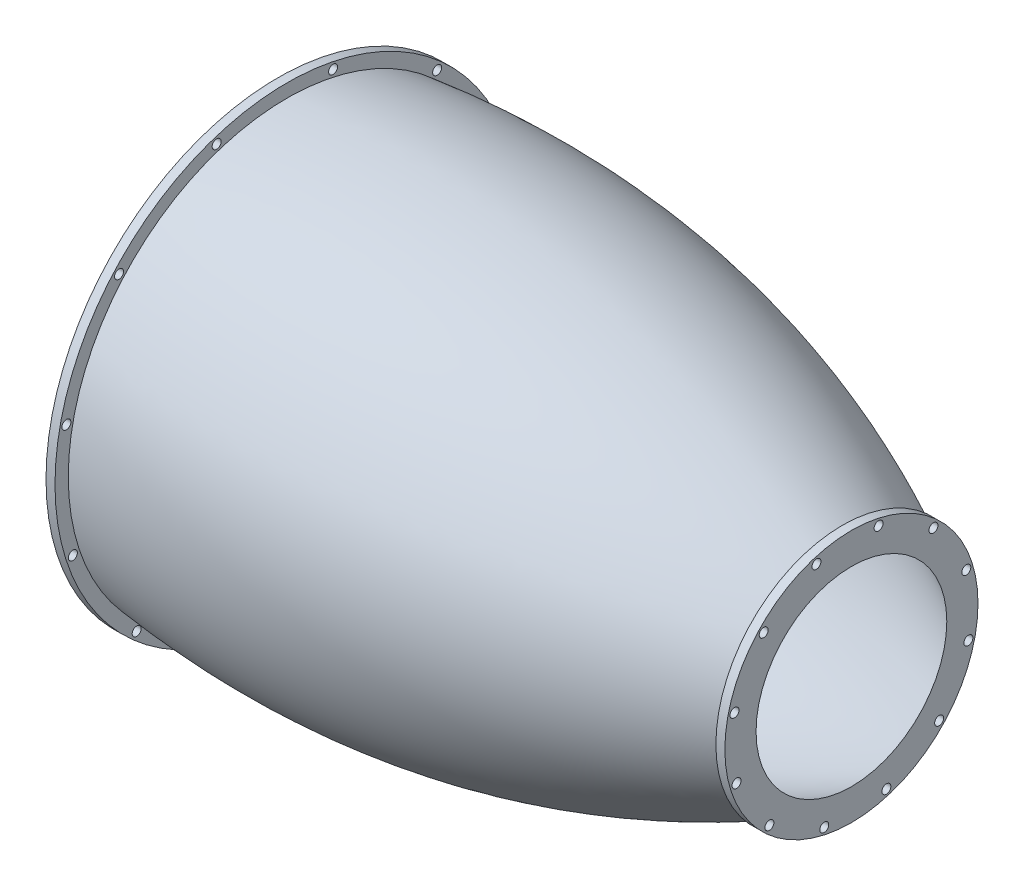
SolidWorks part; units mm, degrees
material "Copper"
ref_plane "Front Plane" through (0, 0, 0) normal (0, 0, 1) x (1, 0, 0)
ref_plane "Top Plane" through (0, 0, 0) normal (0, 1, 0) x (1, 0, 0)
ref_plane "Right Plane" through (0, 0, 0) normal (1, 0, 0) x (0, 0, -1)
sketch "Sketch1" plane through (0, 0, 0) normal (0, 0, 1) x (1, 0, 0)
  line L0 (-1229.8282, 0) -> (1426.3964, 0) construction
  line L1 (0, -63.5) -> (0, 63.5) construction
  line L2 (0, 0) -> (500, 0) construction
  line L3 (500, -330.2) -> (500, 330.2) construction
  line L5 (500, 339.09) -> (500, 330.2)
  line L6 (0, -72.39) -> (0, -63.5)
  line L7 (500, -339.09) -> (500, -330.2)
  line L8 (-412.8242, -144.8099) -> (-412.8242, 144.8099) construction
  line L9 (-412.8242, 144.8099) -> (-412.8242, 153.6999)
  line L10 (-412.8242, -144.8099) -> (-412.8242, -153.6999)
  spline S0 degree 2 poles (0, 63.5) (163.7773, 321.6338) (500, 330.2) knots 0 0 0 1 1 1
  spline S1 degree 2 poles (0, -63.5) (163.7773, -321.6338) (500, -330.2) knots 0 0 0 1 1 1
  spline S2 degree 2 poles (0, -72.39) (163.7773, -330.5238) (500, -339.09) knots 0 0 0 1 1 1
  spline S3 degree 2 poles (0, -63.5) (163.7773, -321.6338) (500, -330.2) knots 0 0 0 1 1 1
  spline S4 degree 2 poles (0, 72.39) (163.7773, 330.5238) (500, 339.09) knots 0 0 0 1 1 1
  spline S5 degree 2 poles (0, 63.5) (-192.2835, 162.6782) (-412.8242, 144.8099) knots 0 0 0 1 1 1
  spline S6 degree 2 poles (0, -63.5) (-192.2835, -162.6782) (-412.8242, -144.8099) knots 0 0 0 1 1 1
  spline S7 degree 2 poles (0, -72.39) (-189.3535, -181.7828) (-412.8242, -153.6999) knots 0 0 0 1 1 1
  spline S9 degree 2 poles (0, 72.39) (-189.3535, 181.7828) (-412.8242, 153.6999) knots 0 0 0 1 1 1
  point P8 (0, 0)
  point P14 (500, 0)
  point P22 (-412.8242, 0)
  dimension "D4" = 8.89
  dimension "D1" = 127
  dimension "D2" = 500
  dimension "D3" = 660.4
  dimension "D5" = 8.89
  dimension "D6" = 8.89
  dimension "D7" = 289.6197
revolve "Revolve3" add sketch "Sketch1" angle 360 about L0 region at (490.4648, 334.645, 0)
ref_plane "Plane1" through (0, 0, 0) normal (1, 0, 0) x (0, 0, -1)
ref_plane "Plane2" through (-7.62, 0, 0) normal (-1, 0, 0) x (0, 0, 1)
sketch "Sketch4" plane through (-7.62, 0, 0) normal (-1, 0, 0) x (0, 0, 1)
  line L1 (-1213.2286, 638.9142) -> (1085.9115, 638.9142)
  line L2 (-1213.2286, 638.9142) -> (-1213.2286, -445.9528)
  line L3 (-1213.2286, -445.9528) -> (1085.9115, -445.9528)
  line L4 (1085.9115, 638.9142) -> (1085.9115, -445.9528)
extrude "Cut-Extrude1" cut sketch "Sketch4" against normal blind 782.066
ref_plane "Plane3" through (-7.62, 0, 0) normal (1, 0, 0) x (0, 0, -1)
sketch "Sketch5" plane through (-7.62, 0, 0) normal (1, 0, 0) x (0, 0, -1)
  circle A0 centre (0, 0) radius 76.7288 construction
  circle A1 centre (0, 0) radius 76.7288
  circle A2 centre (0, 0) radius 89.4288
  dimension "D1" = 12.7
extrude "Boss-Extrude1" add sketch "Sketch5" against normal blind 6.35
ref_plane "Plane4" through (-412.8242, 0, 0) normal (-1, 0, 0) x (0, 0, 1)
sketch "Sketch6" plane through (-412.8242, 0, 0) normal (-1, 0, 0) x (0, 0, 1)
  circle A0 centre (0, 0) radius 153.6999 construction
  circle A1 centre (0, 0) radius 153.6999
  circle A2 centre (0, 0) radius 163.8599
  dimension "D1" = 10.16
extrude "Boss-Extrude2" add sketch "Sketch6" against normal blind 6.35 contours A2 | A1
ref_plane "Plane5" through (-13.97, 0, 0) normal (-1, 0, 0) x (0, 0, 1)
sketch "Sketch7" plane through (-13.97, 0, 0) normal (-1, 0, 0) x (0, 0, 1)
  line L0 (0, 0) -> (20.2302, -87.1106) construction
  line L1 (20.2302, -87.1106) -> (18.1534, -78.168) construction
  circle A1 centre (0, 0) radius 89.4288
  circle A2 centre (0, 0) radius 89.4288
  circle A3 centre (0, 0) radius 80.2482 construction
  circle A4 centre (0, 0) radius 80.2482
  point P7 (19.1918, -82.6393)
  dimension "D1" = 0
hole_wizard "1/4 (0.25) Diameter Hole1" positions "3DSketch1" profile "Sketch8" hole size "1/4" standard "ANSI Inch"
sketch3d "3DSketch1"
  point P0 (-13.97, -82.6393, 19.1918)
sketch "Sketch8" plane through (-13.97, -82.6393, 19.1918) normal (0, 1, 0) x (0, 0, 1)
  line L0 (0, 0) -> (0, 8.2577)
  line L1 (0, 8.2577) -> (3.175, 6.35)
  line L2 (3.175, 6.35) -> (3.175, 0)
  line L5 (3.175, 0) -> (0, 0)
  line L10 (0, 8.2577) -> (-3.175, 6.35) construction
  line L11 (0, -6.35) -> (0, 107.95) construction
  dimension "Hole Dia." = 6.35
  dimension "Hole Depth" = 6.35
  dimension "Drill Angle" = 118
pattern_circular "CirPattern1" count 12 over 360 about axis through (-13.97, 0, 0) along (1, 0, 0) of "1/4 (0.25) Diameter Hole1" reverse direction yes
ref_plane "Plane6" through (-406.4742, 0, 0) normal (1, 0, 0) x (0, 0, -1)
sketch "Sketch9" plane through (-406.4742, 0, 0) normal (1, 0, 0) x (0, 0, -1)
  line L0 (0, 0) -> (-33.5856, -160.381) construction
  line L1 (-33.5856, -160.381) -> (-31.6611, -151.1914) construction
  circle A0 centre (0, 0) radius 163.8599 construction
  circle A1 centre (0, 0) radius 163.8599
  circle A2 centre (0, 0) radius 154.4709 construction
  circle A3 centre (0, 0) radius 154.4709
  point P6 (-32.6234, -155.7862)
hole_wizard "1/4 (0.25) Diameter Hole2" positions "3DSketch2" profile "Sketch10" hole size "1/4" standard "ANSI Inch"
sketch3d "3DSketch2"
  point P0 (-406.4742, -155.7862, 32.6234)
sketch "Sketch10" plane through (-406.4742, -155.7862, 32.6234) normal (0, 1, 0) x (0, 0, -1)
  line L0 (0, 0) -> (0, 8.2577)
  line L1 (0, 8.2577) -> (3.175, 6.35)
  line L2 (3.175, 6.35) -> (3.175, 0)
  line L5 (3.175, 0) -> (0, 0)
  line L10 (0, 8.2577) -> (-3.175, 6.35) construction
  line L11 (0, -6.35) -> (0, 107.95) construction
  dimension "Hole Dia." = 6.35
  dimension "Hole Depth" = 6.35
  dimension "Drill Angle" = 118
pattern_circular "CirPattern2" count 12 over 360 about axis through (-406.4742, 0, 0) along (-1, 0, 0) of "1/4 (0.25) Diameter Hole2" reverse direction yes
